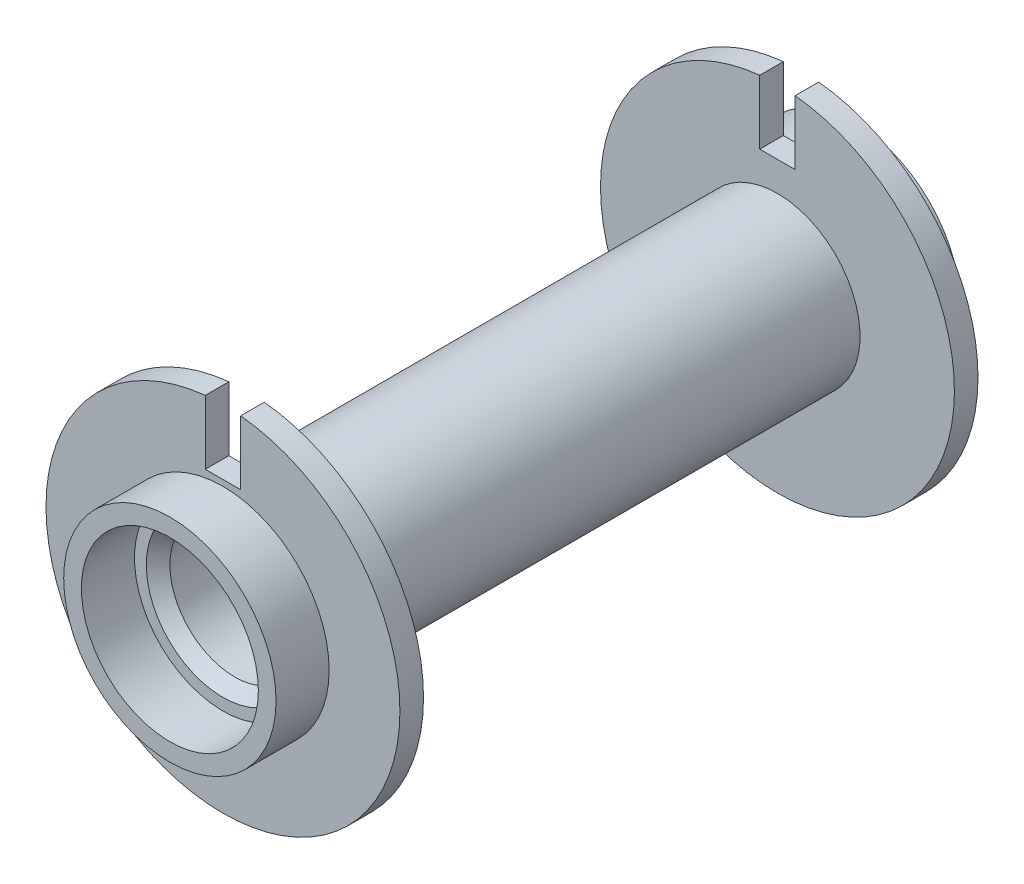
SolidWorks part; units mm, degrees
material "白色 POM"
ref_plane "前视基准面" through (0, 0, 0) normal (0, 0, 1) x (1, 0, 0)
ref_plane "上视基准面" through (0, 0, 0) normal (0, 1, 0) x (1, 0, 0)
ref_plane "右视基准面" through (0, 0, 0) normal (1, 0, 0) x (0, 0, -1)
sketch "草图1" plane through (0, 0, 0) normal (0, 0, 1) x (1, 0, 0)
  circle A0 centre (0, 0) radius 5.5
  circle A1 centre (0, 0) radius 7
  dimension "D1" = 11
  dimension "D2" = 14
extrude "拉伸1" add sketch "草图1" along normal mid plane 59
sketch "草图2" plane through (0, 0, 29.5) normal (0, 0, 1) x (1, 0, 0)
  line L0 (0, 0) -> (0, -11) construction
  line L1 (-10, 11) -> (10, 11) construction
  line L2 (-10, 11) -> (-10, -11) construction
  line L3 (-10, -11) -> (10, -11) construction
  line L4 (10, 11) -> (10, -11) construction
  circle A0 centre (0, 0) radius 5.5 construction
  circle A1 centre (0, 0) radius 5.5
  circle A2 centre (0, 0) radius 15
  dimension "D4" = 30
  dimension "D1" = 11
  dimension "D2" = 22
  dimension "D3" = 20
extrude "拉伸2" add sketch "草图2" against normal blind 7
mirror "镜向1" about plane through (0, 0, 0) normal (0, 0, 1) of "拉伸2"
sketch "草图5" plane through (0, 0, 0) normal (1, 0, 0) x (0, 0, -1)
  line L0 (-29.5, 0) -> (29.5, 0) construction
  line L1 (-29.5, 15) -> (-29.5, -15) construction
  line L2 (29.5, -15) -> (29.5, 15) construction
  line L3 (-29.5, -11) -> (-24, -11)
  line L4 (-24, -11) -> (-24, -20)
  line L5 (24, -11) -> (24, -20)
  line L6 (-29.5, -11) -> (-29.5, -20)
  line L7 (-29.5, -20) -> (-24, -20)
  line L8 (29.5, -11) -> (29.5, -20)
  line L9 (29.5, -20) -> (24, -20)
  line L10 (24, -11) -> (29.5, -11)
  line L12 (-29.5, 15) -> (-29.5, -15) construction
  line L13 (29.5, -15) -> (29.5, 15) construction
  dimension "D1" = 9
  dimension "D2" = 11
  dimension "D4" = 5.5
  dimension "D5" = 5.5
extrude "拉伸4" cut sketch "草图5" against normal mid plane 30
sketch "草图6" plane through (0, -11, 0) normal (0, -1, 0) x (1, 0, 0)
  line L0 (0, 27.5) -> (0, -27.5) construction
  line L1 (-8, 27.5) -> (8, 27.5)
  line L2 (-8, 27.5) -> (-8, -27.5)
  line L3 (-8, -27.5) -> (8, -27.5)
  line L4 (8, 27.5) -> (8, -27.5)
  dimension "D1" = 16
  dimension "D2" = 55
hole_wizard "M3 螺纹孔1" positions "3D草图1" profile "草图7" tap size "M3" standard "GB"
sketch3d "3D草图1"
  point P0 (-8, -11, 27.5)
  point P3 (8, -11, 27.5)
  point P6 (-8, -11, -27.5)
  point P9 (8, -11, -27.5)
sketch "草图7" plane through (-8, -11, 27.5) normal (1, 0, 0) x (0, 0, -1)
  line L0 (0, 0) -> (0, 10.2511)
  line L1 (0, 10.2511) -> (1.25, 9.5)
  line L2 (1.25, 9.5) -> (1.25, 0)
  line L5 (1.25, 0) -> (0, 0)
  line L10 (0, 10.2511) -> (-1.25, 9.5) construction
  line L11 (0, -6.35) -> (0, 107.95) construction
  dimension "螺纹孔钻头直径" = 2.5
  dimension "螺纹孔钻头深度" = 9.5
  dimension "导头角度" = 118
cosmetic thread "孔螺蚊线1" parameters "D1"=8, "D2"=3
cosmetic thread "孔螺蚊线2" parameters "D1"=8, "D2"=3
cosmetic thread "孔螺蚊线3" parameters "D1"=8, "D2"=3
cosmetic thread "孔螺蚊线4" parameters "D1"=8, "D2"=3
chamfer "倒角1" distance 0.5 angle 45 4 edges at (-8, -11, 26.25) (8, -11, 26.25) (8, -11, -28.75) (-8, -11, -28.75)
chamfer "倒角2" distance 2 angle 45 1 edges at (5.5, 0, -29.5)
chamfer "倒角3" [suppressed] distance 1.5 angle 45
sketch "Sketch1" plane through (0, 0, 29.5) normal (0, 0, -1) x (-1, 0, 0)
  circle A0 centre (0, 0) radius 7.5
  dimension "D1" = 15
extrude "Extrude1" cut sketch "Sketch1" along normal blind 5
sketch "Sketch2" plane through (0, 0, -29.5) normal (0, 0, 1) x (1, 0, 0)
  line L0 (0, 0) -> (0, 9) construction
  line L1 (-12.5, 15) -> (12.5, 15)
  line L2 (-12.5, 15) -> (-12.5, 9)
  line L3 (-12.5, 9) -> (12.5, 9)
  line L4 (12.5, 15) -> (12.5, 9)
  dimension "D1" = 25
  dimension "D2" = 9
  dimension "D3" = 6
extrude "Extrude2" cut sketch "Sketch2" along normal up to surface (5.5 mm away) up to face at (0, -13, -24)
chamfer "Chamfer2" distance 2 angle 45 1 edges at (-7.5, 0, 29.5)
sketch "Sketch4" plane through (0, 0, 29.5) normal (0, 0, 1) x (1, 0, 0)
  circle A0 centre (0, 0) radius 17.5
  dimension "D1" = 35
extrude "Extrude3" cut sketch "Sketch4" against normal up to surface (5.5 mm away) up to face at (0, -13, 24)
sketch "Sketch5" plane through (0, 0, -29.5) normal (0, 0, -1) x (-1, 0, 0)
  circle A0 centre (0, 0) radius 17.5
  dimension "D1" = 35
extrude "Extrude4" cut sketch "Sketch5" against normal up to surface (5.5 mm away) up to face at (0, -13, -24)
sketch "Sketch6" plane through (0, 0, 24) normal (0, 0, 1) x (1, 0, 0)
  circle A0 centre (0, 0) radius 7.5
  circle A2 centre (0, 0) radius 9
  dimension "D1" = 15
  dimension "D2" = 18
extrude "Extrude5" add sketch "Sketch6" along normal blind 5
mirror "Mirror1" about plane through (0, 0, 0) normal (0, 0, 1) of "Extrude5"
sketch "Sketch7" plane through (0, 0, 24) normal (0, 0, 1) x (1, 0, 0)
  circle A0 centre (0, 0) radius 15 construction
  circle A1 centre (0, 0) radius 15
  circle A2 centre (0, 0) radius 5.5 construction
  circle A3 centre (0, 0) radius 5.5
extrude "Extrude6" add sketch "Sketch7" along normal blind 0.5
sketch "Sketch8" plane through (0, 0, -24) normal (0, 0, -1) x (-1, 0, 0)
  circle A0 centre (0, 0) radius 15 construction
  circle A1 centre (0, 0) radius 15
  circle A2 centre (0, 0) radius 5.5 construction
  circle A3 centre (0, 0) radius 5.5
extrude "Extrude7" add sketch "Sketch8" along normal blind 0.5
chamfer "Chamfer3" distance 1 angle 45 2 edges at (5.5, 0, 24.5) (-5.5, 0, -24.5)
sketch "Sketch9" plane through (0, 0, 22.5) normal (0, 0, -1) x (-1, 0, 0)
  circle A0 centre (0, 0) radius 15 construction
  circle A1 centre (0, 0) radius 15
  circle A2 centre (0, 0) radius 7 construction
  circle A3 centre (0, 0) radius 7
extrude "Extrude8" [suppressed] add sketch "Sketch9" along normal blind 2 from offset 3
sketch "Sketch10" [suppressed] plane through (0, 0, 18) normal (0, 0, -1) x (-1, 0, 0)
  line L1 (-17, -1) -> (-7, -1)
  line L2 (-17, -1) -> (-17, 1)
  line L3 (-17, 1) -> (-7, 1)
  line L4 (-7, -1) -> (-7, 1)
  circle A0 centre (0, 0) radius 7 construction
  dimension "D1" = 2
  dimension "D2" = 10
extrude "Extrude9" [suppressed] cut sketch "Sketch10" against normal blind 2
sketch "Sketch11" plane through (0, 0, 24.5) normal (0, 0, 1) x (1, 0, 0)
  line L0 (0, 0) -> (0, 9.5) construction
  line L1 (-1.5, 15) -> (1.5, 15)
  line L2 (-1.5, 15) -> (-1.5, 9.5)
  line L3 (-1.5, 9.5) -> (1.5, 9.5)
  line L4 (1.5, 15) -> (1.5, 9.5)
  circle A0 centre (0, 0) radius 15 construction
  dimension "D2" = 5.5
  dimension "D1" = 3
extrude "Extrude10" cut sketch "Sketch11" against normal up to surface (49 mm away) up to face at (-9, 0, -24.5)
